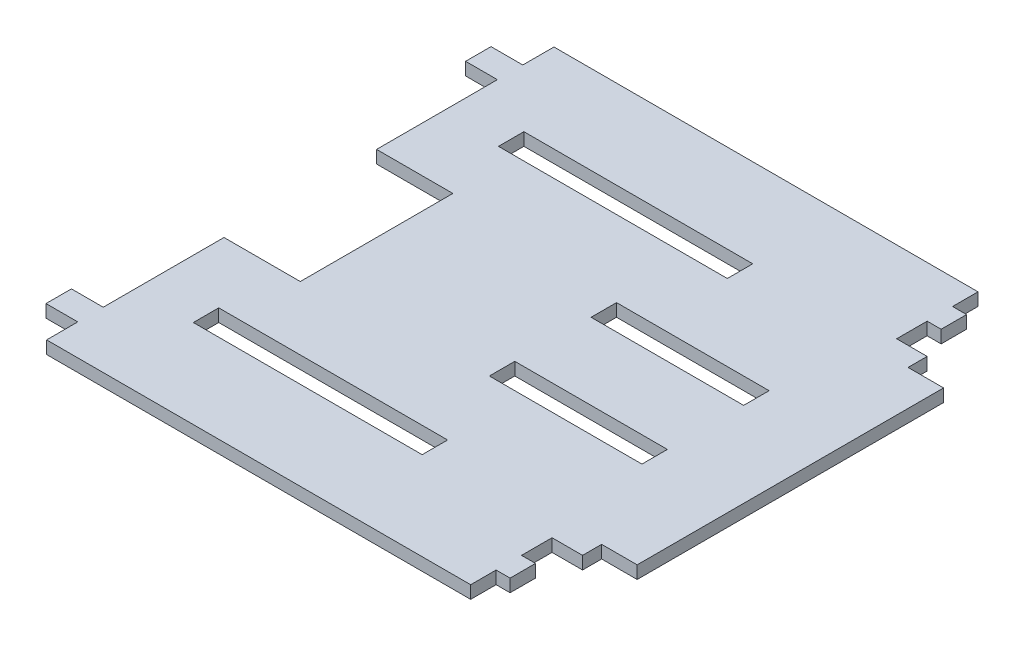
SolidWorks part; units mm, degrees
ref_plane "Alzado" through (0, 0, 0) normal (0, 0, 1) x (1, 0, 0)
ref_plane "Planta" through (0, 0, 0) normal (0, 1, 0) x (1, 0, 0)
ref_plane "Vista lateral" through (0, 0, 0) normal (1, 0, 0) x (0, 0, -1)
sketch "Croquis2" plane through (0, 0, 0) normal (0, 1, 0) x (1, 0, 0)
  line L0 (-81.5023, 77) -> (-92.5023, 77) construction
  line L2 (-92.5023, 88) -> (-81.5023, 88) construction
  line L3 (-81.5023, 97.5) -> (-81.5023, 88) construction
  line L4 (-129.5023, 97.5) -> (-81.5023, 97.5) construction
  line L6 (89.2488, 90.2512) -> (93.2488, 90.2512) construction
  line L7 (89.2488, 99.7512) -> (89.2488, 90.2512) construction
  line L8 (119.2488, 69.7512) -> (119.2488, 99.7512) construction
  line L9 (119.2488, 99.7512) -> (89.2488, 99.7512) construction
  line L10 (-81.5023, 77) -> (-92.5023, 77) construction
  line L11 (-92.5023, 77) -> (-92.5023, 88) construction
  line L12 (-92.5023, 88) -> (-81.5023, 88) construction
  line L13 (-81.5023, 97.5) -> (-81.5023, 88) construction
  line L14 (-129.5023, 97.5) -> (-81.5023, 97.5) construction
  line L15 (93.2488, 90.2512) -> (93.2488, 79.2512) construction
  line L16 (89.2488, 90.2512) -> (93.2488, 90.2512) construction
  line L17 (89.2488, 99.7512) -> (89.2488, 90.2512) construction
  line L18 (119.2488, 69.7512) -> (119.2488, 99.7512) construction
  line L19 (119.2488, 99.7512) -> (89.2488, 99.7512) construction
  line L20 (-222.2523, 0) -> (277.1189, 0) construction
  line L21 (89.2488, 69.7512) -> (99.2488, 69.7512) construction
  line L22 (89.2488, 79.2512) -> (89.2488, 69.7512) construction
  line L23 (93.2488, 79.2512) -> (89.2488, 79.2512) construction
  line L24 (-81.5023, 77) -> (-81.5023, 67.5) construction
  line L25 (89.2488, 69.7512) -> (99.2488, 69.7512) construction
  line L26 (89.2488, 79.2512) -> (89.2488, 69.7512) construction
  line L27 (93.2488, 79.2512) -> (89.2488, 79.2512) construction
  line L28 (-81.5023, 77) -> (-81.5023, 67.5) construction
  line L29 (119.2488, -67.7512) -> (119.2488, 67.7512)
  line L30 (119.2488, 67.7512) -> (87.2488, 67.7512)
  line L31 (87.2488, 67.7512) -> (87.2488, 79.7512)
  line L32 (87.2488, 79.7512) -> (92.7488, 79.7512)
  line L33 (92.7488, 79.7512) -> (92.7488, 89.7512)
  line L34 (92.7488, 89.7512) -> (87.2488, 89.7512)
  line L35 (87.2488, 89.7512) -> (87.2488, 99.7512)
  line L36 (87.2488, 99.7512) -> (-79.5023, 99.7512)
  line L37 (-79.5023, 99.7512) -> (-79.5023, 87.5)
  line L38 (-79.5023, 87.5) -> (-92.0023, 87.5)
  line L39 (-92.0023, 87.5) -> (-92.0023, 77.5)
  line L40 (-92.0023, 77.5) -> (-79.5023, 77.5)
  line L41 (-79.5023, 77.5) -> (-79.5023, 30)
  line L42 (-79.5023, 30) -> (-49.5023, 30)
  line L43 (-49.5023, 30) -> (-49.5023, -30)
  line L44 (-81.5023, -77) -> (-81.5023, -67.5) construction
  line L45 (93.2488, -79.2512) -> (89.2488, -79.2512) construction
  line L46 (89.2488, -79.2512) -> (89.2488, -69.7512) construction
  line L47 (89.2488, -69.7512) -> (99.2488, -69.7512) construction
  line L48 (119.2488, -99.7512) -> (89.2488, -99.7512) construction
  line L49 (119.2488, -69.7512) -> (119.2488, -99.7512) construction
  line L50 (89.2488, -99.7512) -> (89.2488, -90.2512) construction
  line L51 (89.2488, -90.2512) -> (93.2488, -90.2512) construction
  line L52 (93.2488, -90.2512) -> (93.2488, -79.2512) construction
  line L53 (-81.5023, -97.5) -> (-81.5023, -88) construction
  line L54 (-92.5023, -88) -> (-81.5023, -88) construction
  line L55 (-92.5023, -77) -> (-92.5023, -88) construction
  line L56 (-81.5023, -77) -> (-92.5023, -77) construction
  line L57 (-79.5023, -30) -> (-49.5023, -30)
  line L58 (-79.5023, -77.5) -> (-79.5023, -30)
  line L59 (-92.0023, -77.5) -> (-79.5023, -77.5)
  line L60 (-92.0023, -87.5) -> (-92.0023, -77.5)
  line L61 (-79.5023, -87.5) -> (-92.0023, -87.5)
  line L62 (-79.5023, -99.7512) -> (-79.5023, -87.5)
  line L63 (87.2488, -99.7512) -> (-79.5023, -99.7512)
  line L64 (87.2488, -89.7512) -> (87.2488, -99.7512)
  line L65 (92.7488, -89.7512) -> (87.2488, -89.7512)
  line L66 (92.7488, -79.7512) -> (92.7488, -89.7512)
  line L67 (87.2488, -79.7512) -> (92.7488, -79.7512)
  line L68 (87.2488, -67.7512) -> (87.2488, -79.7512)
  line L69 (119.2488, -67.7512) -> (87.2488, -67.7512)
  line L70 (-37.2209, -20) -> (102.5707, -20) construction
  line L71 (-66.264, -60) -> (60.5807, -60) construction
  line L72 (79.8516, 15) -> (19.8516, 15)
  line L73 (79.8516, -25) -> (19.8516, -25)
  line L74 (79.8516, -25) -> (79.8516, -15)
  line L75 (79.8516, -15) -> (19.8516, -15)
  line L76 (19.8516, -25) -> (19.8516, -15)
  line L77 (79.8516, -25) -> (19.8516, -15) construction
  line L78 (79.8516, -15) -> (19.8516, -25) construction
  line L79 (33.4265, -65) -> (-56.5735, -65)
  line L80 (33.4265, -65) -> (33.4265, -55)
  line L81 (33.4265, -55) -> (-56.5735, -55)
  line L82 (-56.5735, -65) -> (-56.5735, -55)
  line L83 (33.4265, -65) -> (-56.5735, -55) construction
  line L84 (33.4265, -55) -> (-56.5735, -65) construction
  line L85 (19.8516, 25) -> (19.8516, 15)
  line L86 (79.8516, 25) -> (19.8516, 25)
  line L87 (79.8516, 25) -> (79.8516, 15)
  line L88 (33.4265, 55) -> (-56.5735, 55)
  line L89 (-56.5735, 65) -> (-56.5735, 55)
  line L90 (33.4265, 65) -> (-56.5735, 65)
  line L91 (33.4265, 65) -> (33.4265, 55)
  point P52 (-49.5023, 0)
  point P65 (119.2488, 0)
  point P68 (49.8516, -20)
  point P73 (-11.5735, -60)
  dimension "D16" = 60
  dimension "D1" = 2
  dimension "D2" = 2
  dimension "D3" = 0.5
  dimension "D4" = 1
  dimension "D5" = 0.5
  dimension "D6" = 2
  dimension "D7" = 2
  dimension "D8" = 0.5
  dimension "D9" = 1
  dimension "D10" = 0.5
  dimension "D11" = 2
  dimension "D12" = 30
  dimension "D13" = 30
  dimension "D14" = 20
  dimension "D15" = 60
  dimension "D17" = 10
  dimension "D18" = 90
  dimension "D19" = 10
extrude "Saliente-Extruir1" add sketch "Croquis2" along normal blind 5
sketch "Croquis3" plane through (0, 0, 0) normal (0, -1, 0) x (1, 0, 0)
  line L7 (89.2488, 69.7512) -> (100.2488, 69.7512) construction
  line L8 (89.2488, -69.7512) -> (100.2488, -69.7512) construction
  line L9 (100.2488, 69.7512) -> (100.2488, 61.25) construction
  line L10 (100.2488, 61.25) -> (114.2126, 61.25) construction
  line L11 (100.2488, -69.7512) -> (100.2488, -61.25) construction
  line L12 (100.2488, -61.25) -> (114.2126, -61.25) construction
  line L13 (114.2126, -61.25) -> (114.2126, 61.25) construction
  line L14 (89.2488, 68.7512) -> (99.2488, 68.7512)
  line L15 (99.2488, 68.7512) -> (99.2488, 60.25)
  line L16 (99.2488, 60.25) -> (113.2126, 60.25)
  line L17 (113.2126, -60.25) -> (113.2126, 60.25)
  line L18 (89.2488, -68.7512) -> (99.2488, -68.7512)
  line L19 (99.2488, -68.7512) -> (99.2488, -60.25)
  line L20 (99.2488, -60.25) -> (113.2126, -60.25)
  line L21 (99.2488, -60.25) -> (114.2126, -60.25) construction
  line L22 (113.2126, -61.25) -> (113.2126, 60.25) construction
  line L23 (89.2488, 68.7512) -> (89.2488, 75.1305)
  line L24 (89.2488, 75.1305) -> (126.7482, 75.1305)
  line L25 (126.7482, 75.1305) -> (126.7482, -74.2656)
  line L26 (126.7482, -74.2656) -> (89.2488, -74.2656)
  line L27 (89.2488, -74.2656) -> (89.2488, -68.7512)
  dimension "D1" = 1
  dimension "D2" = 1
extrude "Cortar-Extruir1" cut sketch "Croquis3" against normal blind 10
